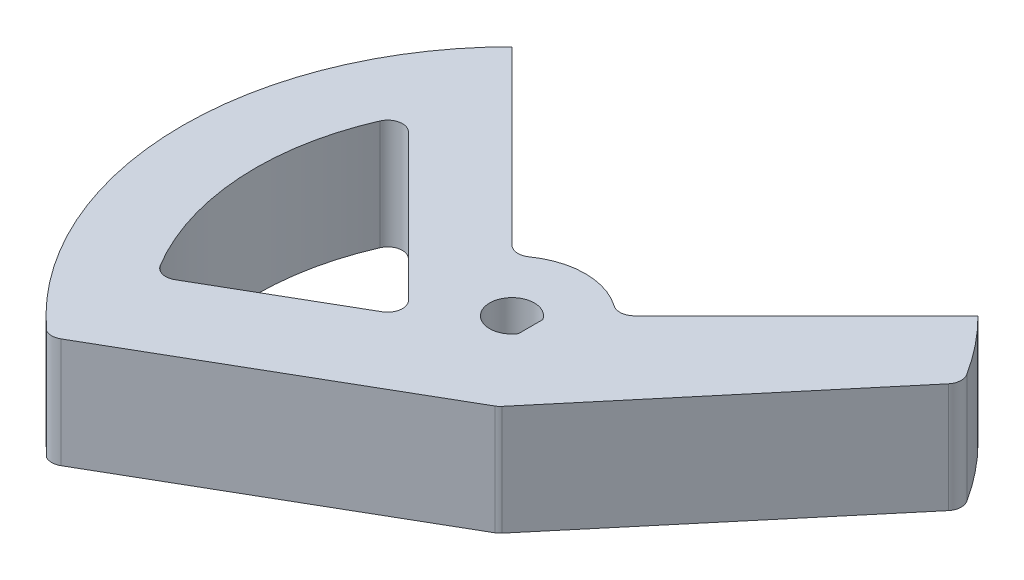
SolidWorks part; units mm, degrees
material "ABS"
ref_plane "Front Plane" through (0, 0, 0) normal (0, 0, 1) x (1, 0, 0)
ref_plane "Top Plane" through (0, 0, 0) normal (0, 1, 0) x (1, 0, 0)
ref_plane "Right Plane" through (0, 0, 0) normal (1, 0, 0) x (0, 0, -1)
sketch "Sketch1" plane through (0, 0, 0) normal (0, 1, 0) x (1, 0, 0)
  line L0 (-31.8198, 31.8198) -> (-7.0711, 7.0711)
  line L1 (7.0711, 7.0711) -> (31.8198, 31.8198)
  line L2 (0, 0) -> (0, 20) construction
  line L3 (0, 0) -> (-7.0711, 7.0711) construction
  line L4 (7.0711, 7.0711) -> (0, 0) construction
  arc A0 (-31.8198, 31.8198) -> (31.8198, 31.8198) centre (0, 0) ccw
  circle A1 centre (0, 0) radius 3
  arc A2 (7.0711, 7.0711) -> (-7.0711, 7.0711) centre (0, 0) ccw
  dimension "D1" = 6
  dimension "D2" = 90
  dimension "D3" = 20
  dimension "D4" = 45
extrude "Boss-Extrude1" add sketch "Sketch1" along normal blind 15
sketch "Sketch2" plane through (0, 15, 0) normal (0, 1, 0) x (1, 0, 0)
  line L0 (2.5, 1.6583) -> (2.5, -1.6583)
  line L1 (-3, 0) -> (-3, -6.6376) construction
  arc A0 (2.5, -1.6583) -> (2.5, 1.6583) centre (0, 0) ccw
  circle A1 centre (0, 0) radius 3 construction
  dimension "D1" = 5.5
extrude "Shaft D" add sketch "Sketch2" against normal up to surface (15 mm away) up to face at (0, 0, -0.9727)
sketch "Sketch3" plane through (0, 15, 0) normal (0, 1, 0) x (1, 0, 0)
  line L0 (-31.8198, 31.8198) -> (-27.5772, 36.0624)
  line L1 (-27.5772, 36.0624) -> (-27.5772, 27.5772)
  line L2 (-7.0711, 7.0711) -> (-31.8198, 31.8198) construction
  line L3 (-27.5772, 27.5772) -> (-31.8198, 31.8198)
  line L4 (0, 0) -> (0, 30.6174) construction
  line L5 (27.5772, 27.5772) -> (31.8198, 31.8198)
  line L6 (27.5772, 36.0624) -> (27.5772, 27.5772)
  line L7 (31.8198, 31.8198) -> (27.5772, 36.0624)
  dimension "D1" = 6
extrude "Boss-Extrude2" [suppressed] add sketch "Sketch3" against normal up to surface (15 mm away) up to face at (0, 0, -0.9727)
sketch "Sketch5" plane through (0, 15, 0) normal (0, 1, 0) x (1, 0, 0)
  line L0 (31.8198, 31.8198) -> (0, 0) construction
  line L1 (0, 0) -> (-31.8198, 31.8198) construction
  line L2 (-31.8198, 31.8198) -> (31.8198, 31.8198) construction
sketch "Sketch4" plane through (0, 15, 0) normal (0, 1, 0) x (1, 0, 0)
  line L0 (-148.943, 0) -> (142.5774, 0) construction
  line L1 (0, 0) -> (-107.5774, -62.1099) construction
  line L2 (0, 0) -> (96.6052, -81.0614) construction
  line L8 (0, 0) -> (81.0614, 96.6052) construction
  line L9 (0, 0) -> (62.1099, -107.5774) construction
  line L10 (-107.5774, -62.1099) -> (62.1099, -107.5774) construction
  line L11 (81.0614, 96.6052) -> (96.6052, -81.0614) construction
  line L14 (11.4907, -9.6418) -> (45.5038, 30.8934)
  line L15 (11.4907, -9.6418) -> (-38.9929, -38.7885)
  arc A2 (-38.9929, -38.7885) -> (45.5038, 30.8934) centre (0, 0) ccw
  dimension "D4" = 55
  dimension "D1" = 40
  dimension "D3" = 30
  dimension "D5" = 15
extrude "Cut-Extrude1" cut sketch "Sketch4" against normal through all
sketch "Sketch6" plane through (7.0477, 0, 12.207) normal (0.5, 0, 0.866) x (0.866, 0, -0.5)
  line L0 (5.1303, 0) -> (-42.7355, 0) construction
  line L1 (-42.7355, 15) -> (5.1303, 15)
  line L2 (-42.7355, 15) -> (-42.7355, 0)
  line L3 (-42.7355, 0) -> (5.1303, 0)
  line L4 (5.1303, 15) -> (5.1303, 0)
  line L5 (-42.7355, 15) -> (5.1303, 0) construction
  line L6 (-42.7355, 0) -> (5.1303, 15) construction
  point P4 (-18.8026, 7.5)
extrude "Boss-Extrude3" add sketch "Sketch6" along normal blind 0.9
sketch "Sketch7" plane through (0, 15, 0) normal (0, 1, 0) x (1, 0, 0)
  line L0 (-30.7882, 16.646) -> (-7.0711, -7.0711)
  line L1 (-7.0711, -7.0711) -> (-28.9338, -19.6935)
  line L2 (11.9407, -10.4212) -> (-29.5123, -34.3541) construction
  line L3 (-7.0711, 7.0711) -> (-31.8198, 31.8198) construction
  arc A0 (-30.7882, 16.646) -> (-28.9338, -19.6935) centre (0, 0) ccw
  dimension "D1" = 35
  dimension "D3" = 10
  dimension "D4" = 12.4072
extrude "Cut-Extrude2" cut sketch "Sketch7" against normal through all contours L0 L1 A0
sketch "Sketch9" plane through (0, 15, 0) normal (0, 1, 0) x (1, 0, 0)
  line L0 (2.5, 1.6583) -> (2.5, -1.6583) construction
  line L1 (2.55, 1.6733) -> (2.55, -1.6733)
  arc A0 (2.5, 1.6583) -> (2.5, -1.6583) centre (0, 0) ccw construction
  arc A1 (2.55, 1.6733) -> (2.55, -1.6733) centre (0, 0) ccw
  dimension "D1" = 0.05
extrude "Shaft Hole Expansion" cut sketch "Sketch9" against normal through all
sketch "Sketch10" plane through (0, 15, 0) normal (0, 1, 0) x (1, 0, 0)
  line L0 (11.4907, -9.6418) -> (7.4934, -14.4056)
  line L1 (7.4934, -14.4056) -> (21.6668, -15.2895)
  line L2 (21.6668, -15.2895) -> (11.4907, -9.6418)
  line L3 (38.7618, 22.8587) -> (11.4907, -9.6418) construction
  line L4 (11.4907, -9.6418) -> (13.8307, -6.8531) construction
extrude "Cut-Extrude4" cut sketch "Sketch10" against normal through all
fillet "Fillet1" radius 2 8 edges at (-28.9338, 7.5, 19.6935) (-30.7882, 7.5, -16.646) (-7.0711, 7.5, 7.0711) (-7.0711, 7.5, -7.0711) (7.0711, 7.5, -7.0711) (-29.5123, 7.5, 34.3541) (9.7992, 7.5, 11.6576) (38.7618, 7.5, -22.8587)
